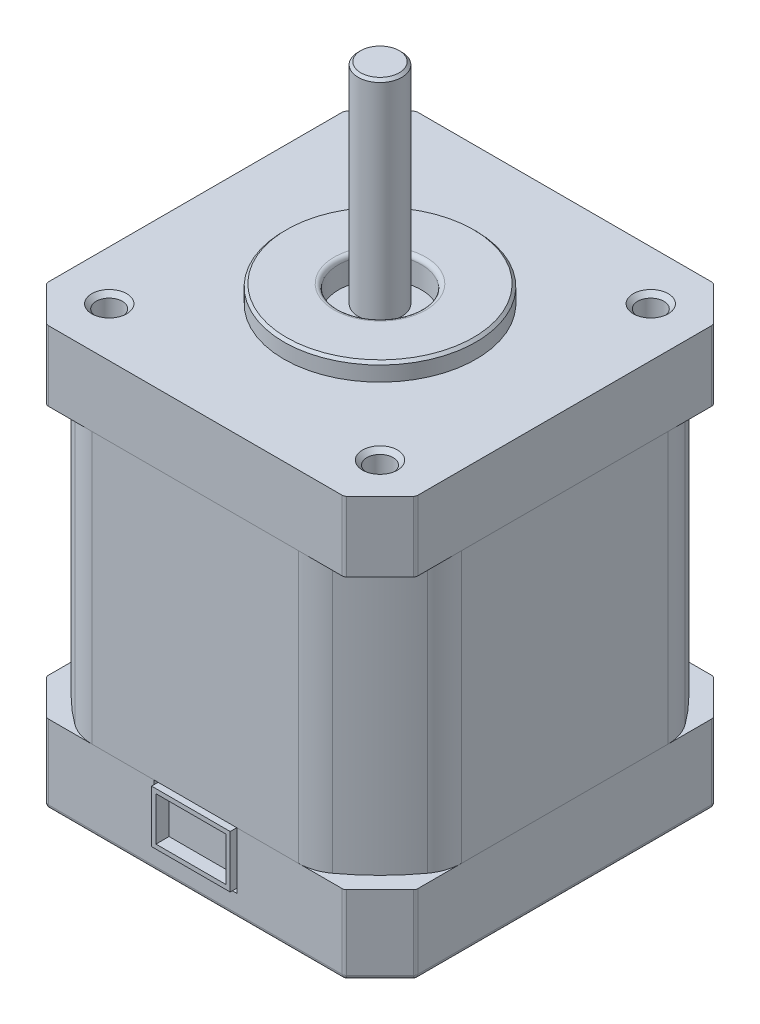
SolidWorks part; units mm, degrees
ref_plane "Спереди" through (0, 0, 0) normal (0, 0, 1) x (1, 0, 0)
ref_plane "Сверху" through (0, 0, 0) normal (0, 1, 0) x (1, 0, 0)
ref_plane "Справа" through (0, 0, 0) normal (1, 0, 0) x (0, 0, -1)
sketch "Эскиз1" plane through (0, 0, 0) normal (0, 1, 0) x (1, 0, 0)
  line L0 (-21.15, 17.0338) -> (-17.0338, 21.15)
  line L1 (-21.15, 21.15) -> (21.15, 21.15)
  line L2 (-21.15, 21.15) -> (-21.15, -21.15)
  line L3 (-21.15, -21.15) -> (21.15, -21.15)
  line L4 (21.15, 21.15) -> (21.15, -21.15)
  line L5 (-21.15, 21.15) -> (21.15, -21.15) construction
  line L6 (-21.15, -21.15) -> (21.15, 21.15) construction
  line L7 (-17.0338, 21.15) -> (17.0338, 21.15)
  line L8 (17.0338, 21.15) -> (21.15, 17.0338)
  line L9 (21.15, 17.0338) -> (21.15, -17.0338)
  line L10 (21.15, -17.0338) -> (17.0338, -21.15)
  line L11 (17.0338, -21.15) -> (-17.0338, -21.15)
  line L12 (-17.0338, -21.15) -> (-21.15, -17.0338)
  point P0 (0, 0)
  dimension "D1" = 42.3
  dimension "D2" = 54
extrude "Бобышка-Вытянуть1" add sketch "Эскиз1" along normal blind 9 contours L12 L3 L10 L4 L8 L1 L0 L2 region at (0, 0, 0)
extrude "Бобышка-Вытянуть2" add sketch "Эскиз1<3>" against normal blind 8 from offset 48 separate body contours L12 L3 L10 L4 L8 L1 L0 L2 region at (0, 0, 0)
sketch "Эскиз1<3>" plane through (0, 0, 0) normal (0, 1, 0) x (1, 0, 0) same geometry as "Эскиз1"
sketch "Эскиз2" plane through (0, 9, 0) normal (0, 1, 0) x (1, 0, 0)
  line L16 (-21.15, -17.0338) -> (-17.0338, -21.15)
  line L17 (-17.0338, -21.15) -> (17.0338, -21.15)
  line L18 (17.0338, -21.15) -> (21.15, -17.0338)
  line L19 (21.15, -17.0338) -> (21.15, 17.0338)
  line L20 (21.15, 17.0338) -> (17.0338, 21.15)
  line L21 (17.0338, 21.15) -> (-17.0338, 21.15)
  line L22 (-17.0338, 21.15) -> (-21.15, 17.0338)
  line L23 (-21.15, 17.0338) -> (-21.15, -17.0338)
  line L25 (-11.7974, -21.15) -> (11.7974, -21.15)
  line L27 (21.15, -11.7974) -> (21.15, 11.7974)
  line L29 (11.7974, 21.15) -> (-11.7974, 21.15)
  line L31 (-21.15, 11.7974) -> (-21.15, -11.7974)
  arc A0 (-20.1875, -14.7467) -> (-14.7467, -20.1875) centre (0, 0) ccw
  arc A1 (-14.7467, 20.1875) -> (-20.1875, 14.7467) centre (0, 0) ccw
  arc A2 (20.1875, 14.7467) -> (14.7467, 20.1875) centre (0, 0) ccw
  arc A3 (14.7467, -20.1875) -> (20.1875, -14.7467) centre (0, 0) ccw
  arc A4 (14.7467, 20.1875) -> (11.7974, 21.15) centre (11.7974, 16.15) ccw
  arc A5 (21.15, 11.7974) -> (20.1875, 14.7467) centre (16.15, 11.7974) ccw
  arc A6 (20.1875, -14.7467) -> (21.15, -11.7974) centre (16.15, -11.7974) ccw
  arc A7 (11.7974, -21.15) -> (14.7467, -20.1875) centre (11.7974, -16.15) ccw
  arc A8 (-14.7467, -20.1875) -> (-11.7974, -21.15) centre (-11.7974, -16.15) ccw
  arc A9 (-20.1875, -14.7467) -> (-21.15, -11.7974) centre (-16.15, -11.7974) cw
  arc A10 (-20.1875, 14.7467) -> (-21.15, 11.7974) centre (-16.15, 11.7974) ccw
  arc A11 (-11.7974, 21.15) -> (-14.7467, 20.1875) centre (-11.7974, 16.15) ccw
  point P22 (21.15, 13.3296)
  point P27 (13.3296, -21.15)
  point P36 (-13.3296, 21.15)
  dimension "D1" = 50
  dimension "D3" = 5
  dimension "D2" = 0
extrude "Бобышка-Вытянуть3" add sketch "Эскиз2" along normal blind 31 separate body
sketch "Эскиз3" plane through (0, 0, 0) normal (0, -1, 0) x (1, 0, 0)
  circle A0 centre (0, 0) radius 4.75
  dimension "D1" = 9.5
extrude "Вырез-Вытянуть1" cut sketch "Эскиз3" against normal blind 3
sketch "Эскиз4" plane through (0, 3, 0) normal (0, -1, 0) x (1, 0, 0)
  circle A0 centre (0, 0) radius 2.5
  circle A1 centre (0, 0) radius 4.75
  dimension "D1" = 5
extrude "Вырез-Вытянуть2" cut sketch "Эскиз4" against normal blind 0.5
sketch "Эскиз5" plane through (0, 3, 0) normal (0, -1, 0) x (1, 0, 0)
  circle A0 centre (0, 0) radius 0.5
  dimension "D1" = 1
extrude "Вырез-Вытянуть3" cut sketch "Эскиз5" against normal blind 0.5
chamfer "Фаска1" distance 0.3 angle 45 1 edges at (0, 3, -2.5)
fillet "Скругление1" radius 0.5 17 edges at (0, 0, 21.15) (19.0919, 0, 19.0919) (21.15, 0, 0) (19.0919, 0, -19.0919) (0, 0, -21.15) (-19.0919, 0, -19.0919) (-21.15, 0, 0) (-19.0919, 0, 19.0919) (0, 0, -4.75) (21.15, 4.5, 17.0338) (17.0338, 4.5, 21.15) (-17.0338, 4.5, 21.15) (-21.15, 4.5, 17.0338) (-21.15, 4.5, -17.0338) (-17.0338, 4.5, -21.15) (17.0338, 4.5, -21.15) (21.15, 4.5, -17.0338)
fillet "Скругление2" radius 0.5 8 edges at (21.15, 44, 17.0338) (17.0338, 44, 21.15) (-17.0338, 44, 21.15) (-21.15, 44, 17.0338) (-21.15, 44, -17.0338) (-17.0338, 44, -21.15) (17.0338, 44, -21.15) (21.15, 44, -17.0338)
sketch "Эскиз6" plane through (0, 48, 0) normal (0, 1, 0) x (1, 0, 0)
  circle A0 centre (0, 0) radius 11
  circle A1 centre (0, 0) radius 4.75
  dimension "D1" = 22
  dimension "D2" = 9.5
extrude "Бобышка-Вытянуть4" add sketch "Эскиз6" along normal blind 2
sketch "Эскиз7" plane through (0, 48, 0) normal (0, 1, 0) x (1, 0, 0)
  circle A2 centre (0, 0) radius 4.75
  circle A3 centre (0, 0) radius 4.75
  dimension "D1" = 0
extrude "Вырез-Вытянуть4" cut sketch "Эскиз7" against normal blind 1
chamfer "Фаска2" distance 0.3 angle 45 1 edges at (0, 50, 11)
fillet "Скругление3" radius 0.5 1 edges at (0, 50, 4.75)
sketch "Эскиз8" plane through (0, 48, 0) normal (0, 1, 0) x (1, 0, 0)
  circle A0 centre (0, 0) radius 2.5
  dimension "D1" = 5
extrude "Бобышка-Вытянуть5" add sketch "Эскиз8" along normal blind 24
chamfer "Фаска4" distance 0.3 angle 45 1 edges at (0, 72, 2.5)
sketch "Эскиз10" plane through (0, 0, 21.15) normal (0, 0, 1) x (1, 0, 0)
  line L0 (0, 0) -> (0, 9) construction
  line L1 (-11.7974, 9) -> (11.7974, 9) construction
  line L2 (-16.8267, 9) -> (16.8267, 9) construction
  line L3 (-4.75, 2.5) -> (4.75, 2.5)
  line L4 (-4.75, 2.5) -> (-4.75, 9)
  line L5 (-4.75, 9) -> (4.75, 9)
  line L6 (4.75, 2.5) -> (4.75, 9)
  line L7 (-4.75, 2.5) -> (4.75, 9) construction
  line L8 (-4.75, 9) -> (4.75, 2.5) construction
  point P5 (0, 5.75)
  dimension "D1" = 9.5
  dimension "D2" = 6.5
extrude "Вырез-Вытянуть6" cut sketch "Эскиз10" against normal blind 1
sketch "Эскиз11" plane through (0, 0, 20.15) normal (0, 0, 1) x (1, 0, 0)
  line L8 (4.5, 2.75) -> (4.5, 8.75)
  line L9 (4.5, 8.75) -> (-4.5, 8.75)
  line L10 (-4.5, 8.75) -> (-4.5, 2.75)
  line L11 (-4.5, 2.75) -> (4.5, 2.75)
  line L12 (4.5, 2.75) -> (4.5, 8.75)
  line L13 (4.5, 8.75) -> (-4.5, 8.75)
  line L14 (-4.5, 8.75) -> (-4.5, 2.75)
  line L15 (-4.5, 2.75) -> (4.5, 2.75)
  line L20 (4, 3.25) -> (4, 8.25)
  line L21 (4, 8.25) -> (-4, 8.25)
  line L22 (-4, 8.25) -> (-4, 3.25)
  line L23 (-4, 3.25) -> (4, 3.25)
  line L24 (4, 3.25) -> (4, 8.25)
  line L25 (4, 8.25) -> (-4, 8.25)
  line L26 (-4, 8.25) -> (-4, 3.25)
  line L27 (-4, 3.25) -> (4, 3.25)
  dimension "D1" = 0.25
  dimension "D2" = 0.75
extrude "Бобышка-Вытянуть6" add sketch "Эскиз11" along normal blind 1.5 separate body
sketch "Эскиз16" plane through (0, 48, 0) normal (0, 1, 0) x (1, 0, 0)
  line L1 (-15.5, 15.5) -> (15.5, 15.5) construction
  line L2 (-15.5, 15.5) -> (-15.5, -15.5) construction
  line L3 (-15.5, -15.5) -> (15.5, -15.5) construction
  line L4 (15.5, 15.5) -> (15.5, -15.5) construction
  line L5 (-15.5, 15.5) -> (15.5, -15.5) construction
  line L6 (-15.5, -15.5) -> (15.5, 15.5) construction
  circle A0 centre (-15.5, 15.5) radius 1.5
  circle A1 centre (15.5, 15.5) radius 1.5
  circle A2 centre (15.5, -15.5) radius 1.5
  circle A3 centre (-15.5, -15.5) radius 1.5
  point P0 (0, 0)
  dimension "D1" = 3
  dimension "D2" = 31
extrude "Вырез-Вытянуть9" cut sketch "Эскиз16" against normal blind 7
chamfer "Фаска35" distance 0.5 angle 45 4 edges at (-15.5, 48, 17) (15.5, 48, 17) (15.5, 48, -14) (-15.5, 48, -14)
